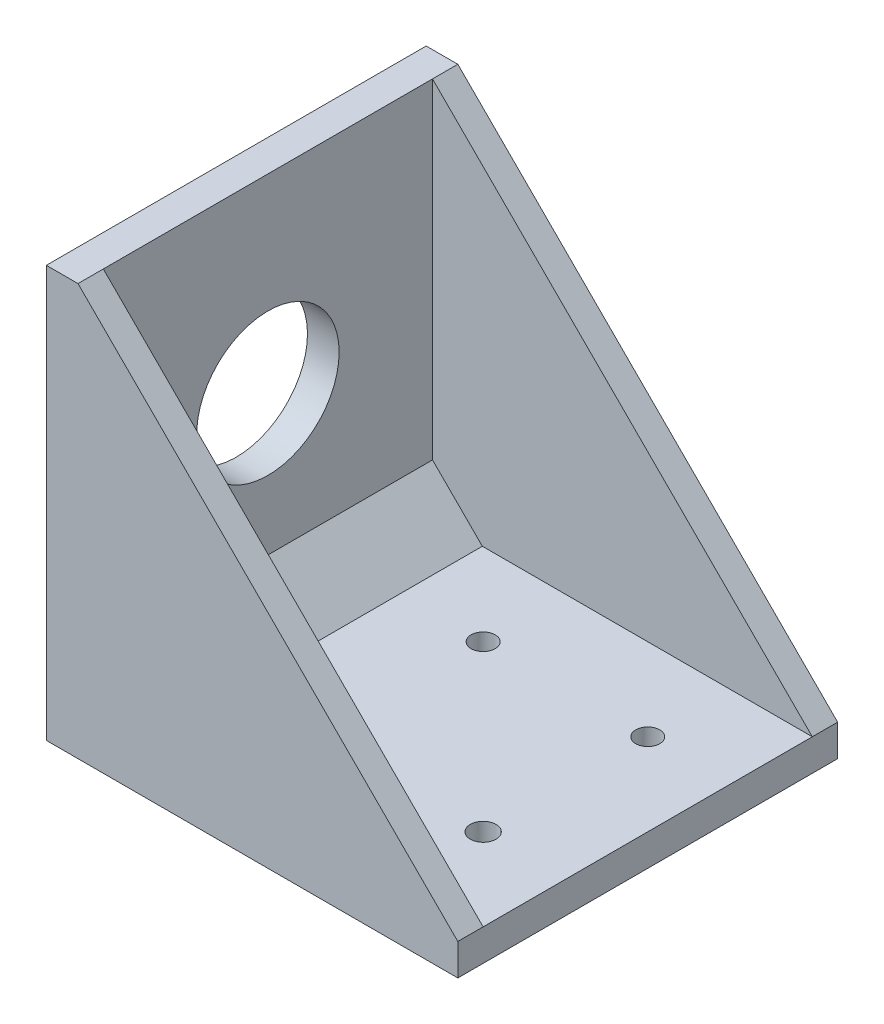
SolidWorks part; units mm, degrees
ref_plane "Front Plane" through (0, 0, 0) normal (0, 0, 1) x (1, 0, 0)
ref_plane "Top Plane" through (0, 0, 0) normal (0, 1, 0) x (1, 0, 0)
ref_plane "Right Plane" through (0, 0, 0) normal (1, 0, 0) x (0, 0, -1)
sketch "Sketch1" plane through (0, 0, 0) normal (1, 0, 0) x (0, 0, -1)
  line L5 (38.1, 38.1) -> (-38.1, 38.1)
  line L6 (38.1, 38.1) -> (38.1, -38.1)
  line L7 (38.1, -38.1) -> (-38.1, -38.1)
  line L8 (-38.1, 38.1) -> (-38.1, -38.1)
  line L9 (38.1, 38.1) -> (-38.1, -38.1) construction
  line L10 (38.1, -38.1) -> (-38.1, 38.1) construction
  line L11 (-38.1, -38.1) -> (38.1, -38.1)
  line L12 (-38.1, -38.1) -> (-38.1, -44.45)
  line L13 (-38.1, -44.45) -> (38.1, -44.45)
  line L14 (38.1, -38.1) -> (38.1, -44.45)
  circle A2 centre (0, 0) radius 14.2875
  dimension "D1" = 28.575
  dimension "D2" = 76.2
  dimension "D3" = 76.2
  dimension "D4" = 6.35
extrude "Boss-Extrude1" add sketch "Sketch1" along normal blind 76.2 contours L14 L7 L12 L13 region at (0, -41.275, 0)
extrude "Boss-Extrude2" add sketch "Sketch1<3>" against normal blind 6.35 separate body contours L5 L8 L7 L6 A2 region at (0, 0, -37.0224)
sketch "Sketch1<3>" plane through (0, 0, 0) normal (1, 0, 0) x (0, 0, -1) same geometry as "Sketch1"
sketch "Sketch3" plane through (0, -38.1, 0) normal (0, -1, 0) x (1, 0, 0)
  line L1 (-6.35, -38.1) -> (0, -38.1)
  line L2 (-6.35, -38.1) -> (-6.35, 38.1)
  line L3 (-6.35, 38.1) -> (0, 38.1)
  line L4 (0, -38.1) -> (0, 38.1)
extrude "Boss-Extrude3" add sketch "Sketch3" along normal blind 6.35 contours L2 L1 L4 L3
sketch "Sketch4" plane through (0, 0, 38.1) normal (0, 0, 1) x (1, 0, 0)
  line L0 (0, 38.1) -> (76.2, -38.1)
  line L1 (76.2, -38.1) -> (0, -38.1)
  line L2 (0, -38.1) -> (0, 38.1)
extrude "Boss-Extrude4" add sketch "Sketch4" against normal blind 5.08 contours L2 L0 L1
sketch "Sketch5" plane through (0, 0, -38.1) normal (0, 0, -1) x (-1, 0, 0)
  line L0 (0, 38.1) -> (-76.2, -38.1)
  line L1 (-76.2, -38.1) -> (0, -38.1)
  line L2 (0, -38.1) -> (0, 38.1)
extrude "Boss-Extrude5" add sketch "Sketch5" against normal blind 5.08
chamfer "Chamfer2" distance 10 angle 45 1 edges at (0, -38.1, 0)
sketch "Sketch6" plane through (0, -38.1, 0) normal (0, 1, 0) x (1, 0, 0)
  line L2 (76.2, 33.02) -> (76.2, -33.02) construction
  line L3 (76.2, -33.02) -> (10, -33.02) construction
  line L4 (76.2, 33.02) -> (10, 33.02) construction
  circle A0 centre (26.67, 16.51) radius 2.413
  circle A1 centre (59.69, 16.51) radius 2.413
  circle A2 centre (26.67, -16.51) radius 2.413
  circle A3 centre (59.69, -16.51) radius 2.5797
  point P8 (0, 0)
  dimension "D1" = 4.826
  dimension "D2" = 4.826
  dimension "D3" = 4.826
  dimension "D4" = 5.1594
  dimension "D5" = 16.51
  dimension "D6" = 49.53
  dimension "D7" = 16.51
  dimension "D9" = 16.51
  dimension "D10" = 16.51
  dimension "D11" = 16.51
  dimension "D12" = 16.51
  dimension "D8" = 49.53
extrude "Cut-Extrude1" cut sketch "Sketch6" against normal through all contours A2 | A3 | A1 | A0 region at (26.67, -38.1, 16.51) region at (59.69, -38.1, 16.51)
